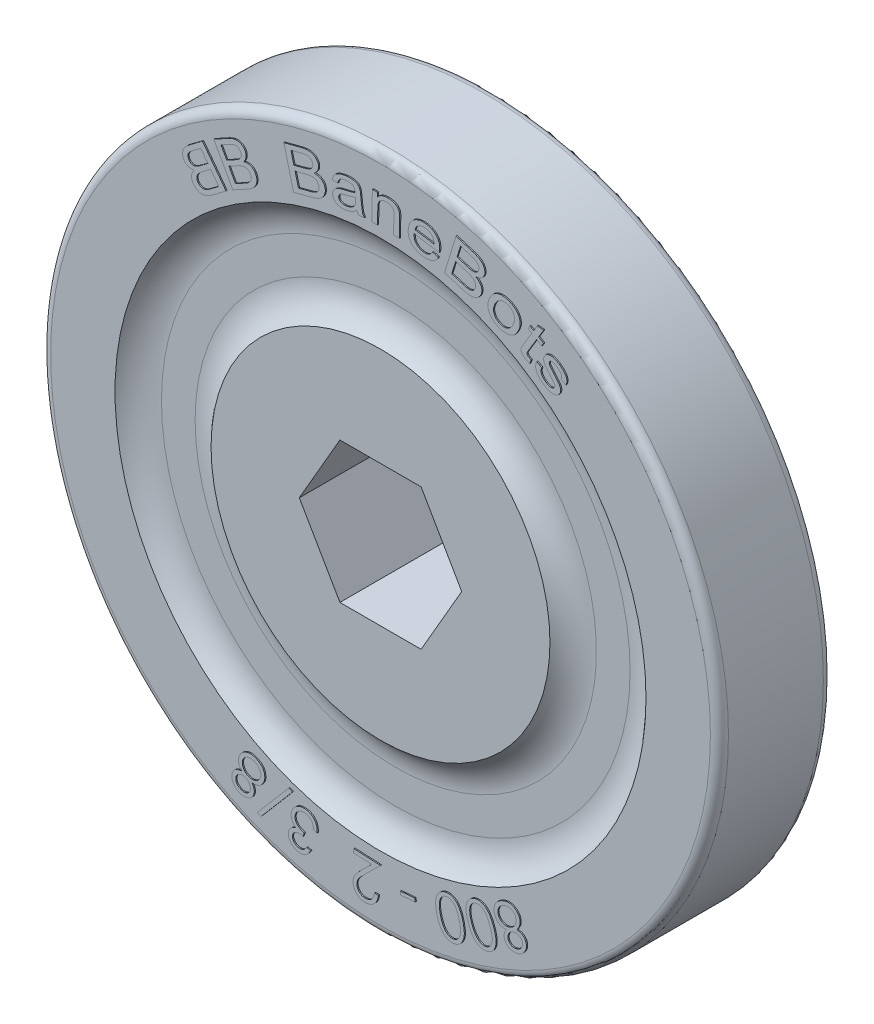
SolidWorks part; units mm, degrees
ref_plane "Front Plane" through (0, 0, 0) normal (0, 0, 1) x (1, 0, 0)
ref_plane "Top Plane" through (0, 0, 0) normal (0, 1, 0) x (1, 0, 0)
ref_plane "Right Plane" through (0, 0, 0) normal (1, 0, 0) x (0, 0, -1)
sketch "Sketch1" plane through (0, 0, 0) normal (0, 0, 1) x (1, 0, 0)
  line L1 (3.594, -6.225) -> (7.188, 0)
  line L2 (7.188, 0) -> (3.594, 6.225)
  line L3 (3.594, 6.225) -> (-3.594, 6.225)
  line L4 (-3.594, 6.225) -> (-7.188, 0)
  line L5 (-7.188, 0) -> (-3.594, -6.225)
  line L6 (-3.594, -6.225) -> (3.594, -6.225)
  circle A0 centre (0, 0) radius 6.225 construction
  circle A1 centre (0, 0) radius 30
  dimension "D1" = 12.45
  dimension "D2" = 60
extrude "Extrude1" add sketch "Sketch1" along normal mid plane 10
fillet "Fillet1" radius 0.8 2 edges at (30, 0, -5) (30, 0, 5)
sketch "Sketch2" plane through (0, 0, 0) normal (0, 1, 0) x (1, 0, 0)
  line L0 (0, 10.15) -> (0, 8.65)
  line L1 (0, 8.65) -> (-15, 8.65)
  line L2 (-15, 8.65) -> (-15, 3.65)
  line L3 (-15, 3.65) -> (-23.5, 3.65)
  line L4 (-23.5, 3.65) -> (-23.5, 10.14)
  line L5 (-23.5, 10.14) -> (-28.5, 10.14)
  line L6 (-28.5, 10.14) -> (-28.5, 10.15)
  line L8 (-28.5, 10.15) -> (0, 10.15)
  dimension "D1" = 0.01
  dimension "D2" = 15
  dimension "D3" = 23.5
  dimension "D4" = 6.5
  dimension "D5" = 1.5
  dimension "D6" = 28.5
revolve "Cut-Revolve1" cut sketch "Sketch2" angle 360 about L0
fillet "Fillet3" radius 3.5 2 edges at (-15, 0, -3.65) (-23.5, 0, -3.65)
sketch "Sketch4" plane through (0, 0, -5) normal (0, 0, -1) x (-1, 0, 0)
  line L0 (0, 0) -> (-8.5001, 22.9782) construction
  line L1 (-13.2866, 20.5843) -> (-15.8355, 24.5332) construction
  line L3 (0, 0) -> (16.091, 18.4751) construction
  line L4 (0, 0) -> (0, 28.5) construction
  line L5 (0, 0) -> (-16.091, 18.4751) construction
  line L6 (0, -24.5) -> (0, 0) construction
  arc A0 (16.091, 18.4751) -> (-8.5001, 22.9782) centre (0, 0) ccw construction
  arc A1 (-10.2097, 22.2713) -> (-16.091, 18.4751) centre (0, 0) ccw construction
  circle A2 centre (0, 0) radius 29.2 construction
  arc A5 (12.7, -20.9514) -> (-12.7, -20.9514) centre (0, 0) cw construction
  text T0 "BaneBots" font "Arial" height 3.5
  text T1 "800 - 2  3/8"
  dimension "D1" = 49
  dimension "D2" = 25
  dimension "D3" = 7
  dimension "D4" = 1.85
  dimension "D5" = 25.4
extrude "Extrude3" add sketch "Sketch4" along normal blind 0.1
mirror "Mirror1" about plane through (0, 0, 0) normal (0, 0, 1) of "Cut-Revolve1", "Fillet3"
sketch "Sketch5" plane through (0, 0, -5) normal (0, 0, -1) x (-1, 0, 0)
  text T0 "B" font "Arial" height 3.5
extrude "Extrude4" add sketch "Sketch5" along normal blind 0.1
ref_plane "Plane1" through (0, 0, 0) normal (0.8402, -0.5423, 0) x (0, 0, -1)
mirror "Mirror2" about plane through (0, 0, 0) normal (0.8402, -0.5423, 0) of "Extrude4"
sketch "Sketch6" plane through (0, 0, 5) normal (0, 0, 1) x (1, 0, 0)
  line L0 (0, 0) -> (0, 28.5) construction
  arc A0 (-16.091, 18.4751) -> (-10.2097, 22.2713) centre (0, 0) cw construction
  arc A1 (8.5001, 22.9782) -> (-16.091, 18.4751) centre (0, 0) ccw construction
  arc A2 (16.091, 18.4751) -> (-8.5001, 22.9782) centre (0, 0) ccw construction
  arc A6 (-12.7, -20.9514) -> (12.7, -20.9514) centre (0, 0) ccw
  arc A7 (-12.7, -20.9514) -> (12.7, -20.9514) centre (0, 0) ccw construction
  text T0 "BaneBots" font "Arial" height 3.5
  text T1 "800 - 2  3/8" font "Century Gothic" height 3.5
  dimension "D1" = 7
  dimension "D3" = 0
  dimension "D2" = 25
extrude "Extrude5" add sketch "Sketch6" along normal blind 0.1
sketch "Sketch7" plane through (0, 0, 5) normal (0, 0, 1) x (1, 0, 0)
  line L0 (-13.2866, 20.5843) -> (-15.8355, 24.5332) construction
  arc A2 (-10.2097, 22.2713) -> (-16.091, 18.4751) centre (0, 0) ccw construction
  circle A3 centre (0, 0) radius 29.2 construction
  text T0 "B" font "Arial" height 3.5
extrude "Extrude6" add sketch "Sketch7" along normal blind 0.1
ref_plane "Plane2" through (0, 0, 0) normal (0.8402, 0.5423, 0) x (0, 0, -1)
mirror "Mirror3" about plane through (0, 0, 0) normal (0.8402, 0.5423, 0) of "Extrude6"
